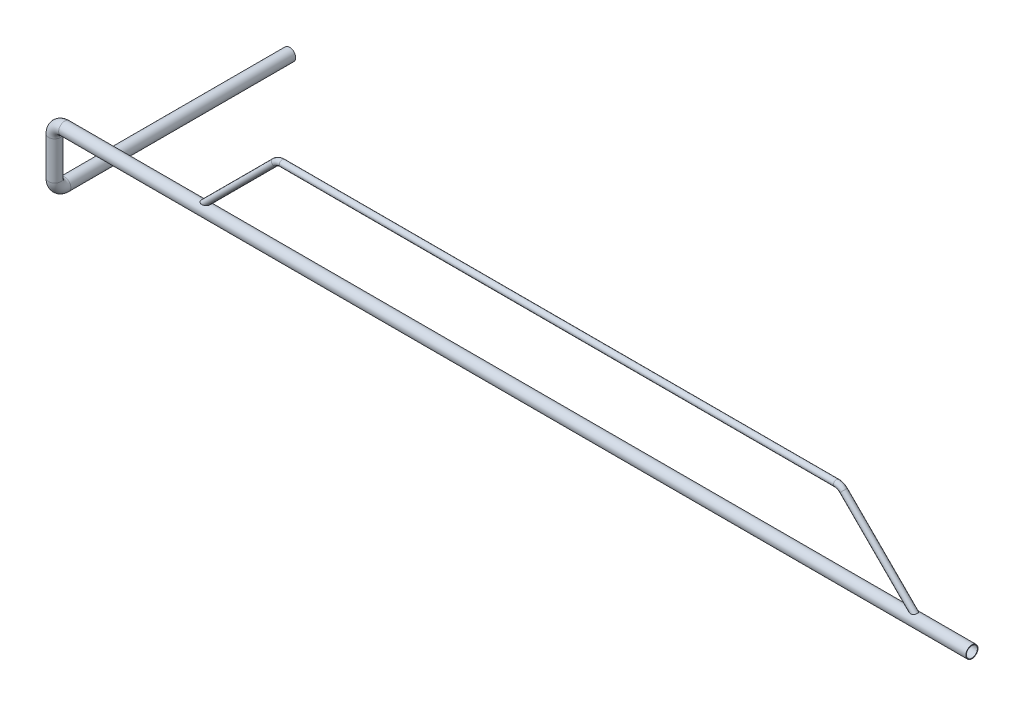
SolidWorks part; units mm, degrees
ref_plane "Plano frontal" through (0, 0, 0) normal (0, 0, 1) x (1, 0, 0)
ref_plane "Plano superior" through (0, 0, 0) normal (0, 1, 0) x (1, 0, 0)
ref_plane "Plano direito" through (0, 0, 0) normal (1, 0, 0) x (0, 0, -1)
sketch3d "3DSketch1"
  line L0 (-24895.3928, -8331.3874, 39894.9033) -> (-29366.5577, -8331.3874, 39894.9033)
  line L1 (-29416.5577, -8381.3874, 39894.9033) -> (-29416.5577, -8570.2286, 39894.9033)
  line L2 (-29416.5577, -8620.2286, 39844.9033) -> (-29416.5577, -8620.2286, 38736.7002)
  line L3 (-29416.5577, -8620.2286, 38736.7002) -> (-29416.5577, -8620.2286, 38707.7002) construction
  circle A0 centre (-24895.3928, -8331.3874, 39894.9033) radius 26.2509 construction
  arc A1 (-29416.5577, -8620.2286, 39844.9033) -> (-29416.5577, -8570.2286, 39894.9033) centre (-29416.5577, -8570.2286, 39844.9033) ccw
  arc A2 (-29416.5577, -8381.3874, 39894.9033) -> (-29366.5577, -8331.3874, 39894.9033) centre (-29366.5577, -8381.3874, 39894.9033) ccw
  point P4 (-24869.1419, -8331.3874, 39894.9033)
  point P13 (-29416.5577, -8620.2286, 39894.9033)
  point P14 (-29466.5577, -8570.2286, 39844.9033)
  point P17 (-29416.5577, -8331.3874, 39894.9033)
  point P18 (-29366.5577, -8381.3874, 39844.9033)
  dimension "D1" = 50
sweep "Sweep-Thin1" add path "3DSketch1" circular profile diameter 60 parameters "D1"=3, "D3"=60
sketch3d "3DSketch2"
  line L0 (-25155.0561, -8331.3874, 39894.9033) -> (-25527.6899, -7958.7537, 39894.9033)
  line L1 (-24895.3928, -8331.3874, 39894.9033) -> (-29366.5577, -8331.3874, 39894.9033) construction
  line L2 (-25563.0452, -7944.109, 39894.9033) -> (-28294.2298, -7944.109, 39894.9033)
  line L3 (-28329.5852, -7958.7537, 39894.9033) -> (-28702.219, -8331.3874, 39894.9033)
  line L4 (-25686.4906, -7944.109, 39894.9033) -> (-25686.4906, -8331.3874, 39894.9033) construction
  arc A0 (-28294.2298, -7944.109, 39894.9033) -> (-28329.5852, -7958.7537, 39894.9033) centre (-28294.2298, -7994.109, 39894.9033) ccw
  arc A1 (-25563.0452, -7944.109, 39894.9033) -> (-25527.6899, -7958.7537, 39894.9033) centre (-25563.0452, -7994.109, 39894.9033) ccw
  point P10 (-28314.9405, -7944.109, 39894.9033)
  point P11 (-28294.2298, -7994.109, 39944.9033)
  point P14 (-25542.3346, -7944.109, 39894.9033)
  point P15 (-25563.0452, -7994.109, 39844.9033)
  dimension "D3" = 50
  dimension "D1" = 135
  dimension "D2" = 135
sweep "Sweep-Thin2" add path "3DSketch2" circular profile diameter 30 parameters "D1"=3, "D3"=30
